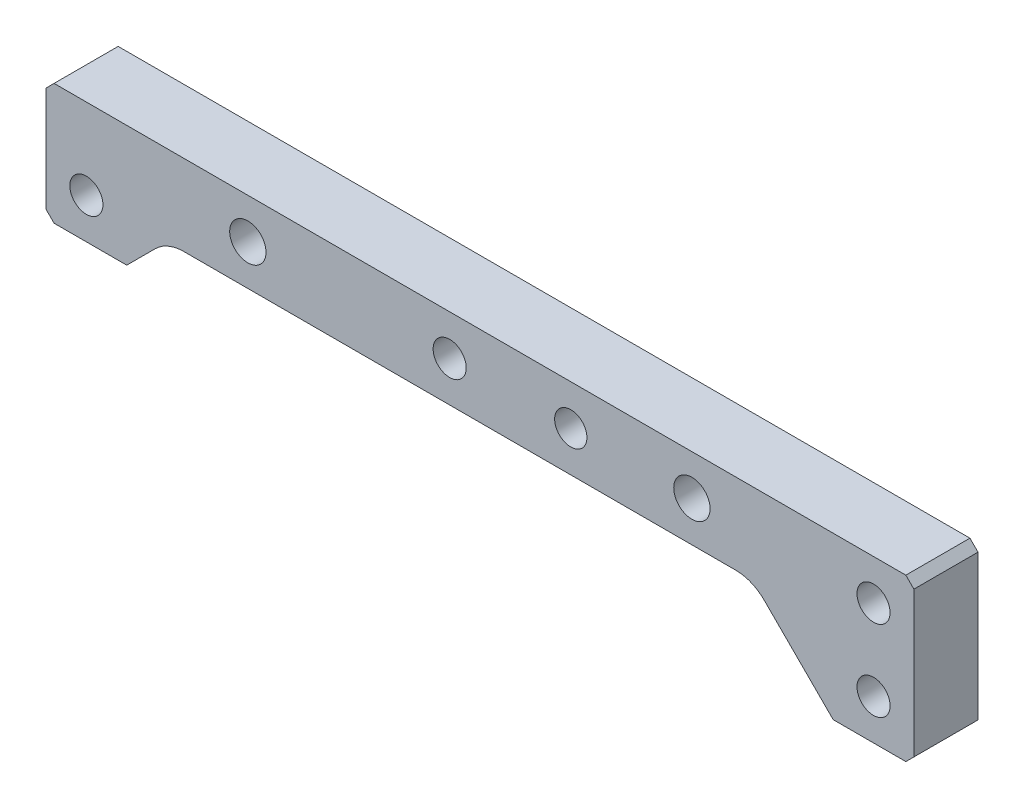
SolidWorks part; units mm, degrees
ref_plane "前视基准面" through (0, 0, 0) normal (0, 0, 1) x (1, 0, 0)
ref_plane "上视基准面" through (0, 0, 0) normal (0, 1, 0) x (1, 0, 0)
ref_plane "右视基准面" through (0, 0, 0) normal (1, 0, 0) x (0, 0, -1)
sketch "草图1" plane through (0, 0, 0) normal (0, 0, 1) x (1, 0, 0)
  line L0 (0, 0) -> (-30, 0) construction
  line L1 (0, 0) -> (0, 10) construction
  line L3 (45, 10) -> (-45, 10) construction
  line L8 (0, 10) -> (-130, 10)
  line L9 (-130, 10) -> (-130, -20)
  line L15 (0, -10) -> (-110, -10)
  line L20 (0, 0) -> (0, -10) construction
  line L21 (-110, -10) -> (-110, -20)
  line L22 (75, 0) -> (75, -20) construction
  line L24 (85, 10) -> (85, -30)
  line L25 (85, -30) -> (65, -30)
  line L26 (65, -30) -> (65, -10)
  line L29 (-110, -20) -> (-130, -20)
  line L30 (-110, -10) -> (-120, -10) construction
  line L31 (0, 10) -> (85, 10)
  line L32 (65, -10) -> (0, -10)
  circle A0 centre (0, 0) radius 4
  circle A1 centre (-30, 0) radius 4.1
  circle A4 centre (75, 0) radius 4.1
  circle A5 centre (75, -20) radius 4.1
  circle A6 centre (-120, -10) radius 4.1
  dimension "D1" = 130
  dimension "D5" = 40
  dimension "D2" = 30
  dimension "D3" = 10
  dimension "D4" = 10
  dimension "D6" = 85
  dimension "D7" = 20
extrude "凸台-拉伸1" add sketch "草图1" along normal blind 15.875
chamfer "倒角1" distance 2 angle 45 4 edges at (-130, 10, 7.9375) (-130, -20, 7.9375) (85, -30, 7.9375) (85, 10, 7.9375)
sketch "草图2" plane through (0, 0, 0) normal (0, 0, -1) x (-1, 0, 0)
  line L0 (0, 0) -> (-30, 0) construction
  circle A0 centre (-30, 0) radius 4.5
extrude "切除-拉伸1" cut sketch "草图2" against normal blind 20
sketch "草图3" plane through (0, 0, 0) normal (0, 0, -1) x (-1, 0, 0)
  line L0 (30, 0) -> (80, 0) construction
  circle A0 centre (80, 0) radius 4.5
extrude "切除-拉伸2" cut sketch "草图3" against normal blind 20
chamfer "倒角2" distance 20 angle 45 1 edges at (65, -10, 7.9375)
chamfer "倒角3" distance 10 angle 45 1 edges at (-110, -10, 7.9375)
fillet "圆角1" radius 10 2 edges at (-100, -10, 7.9375) (45, -10, 7.9375)
